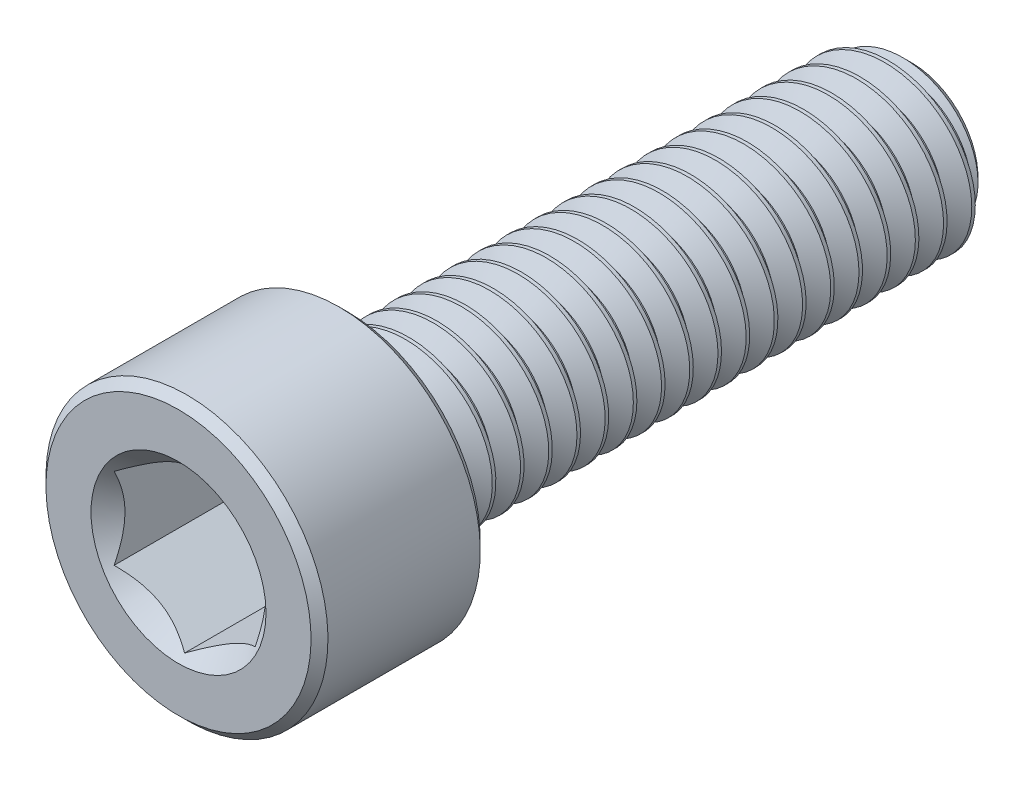
SolidWorks part; units mm, degrees
ref_plane "Front Plane" through (0, 0, 0) normal (0, 0, 1) x (1, 0, 0)
ref_plane "Top Plane" through (0, 0, 0) normal (0, 1, 0) x (1, 0, 0)
ref_plane "Right Plane" through (0, 0, 0) normal (1, 0, 0) x (0, 0, -1)
sketch "Sketch1" plane through (0, 0, 0) normal (1, 0, 0) x (0, 0, -1)
  line L0 (-13, 0) -> (13, 0) construction
  line L1 (13, 0) -> (13, 2.3505) construction
  line L2 (13, 2.3505) -> (12.3505, 3) construction
  line L3 (12.3505, 3) -> (12.25, 3) construction
  line L4 (12.25, 3) -> (-7, 3) construction
  line L5 (-7, 3) -> (-7, 5) construction
  line L6 (-7, 5) -> (-13, 5) construction
  line L7 (-13, 5) -> (-13, 0) construction
  line L8 (13, 2.3505) -> (13, 3) construction
  line L9 (12.9375, 3.1083) -> (13.4375, 2.2422) construction
  line L10 (13.4375, 2.2422) -> (13.9375, 3.1083) construction
  line L11 (13.9375, 3.1083) -> (12.9375, 3.1083) construction
  line L12 (13.4375, 3.1083) -> (13.4375, 3) construction
  line L13 (13.4375, 2.2422) -> (13.4375, 2.3505) construction
  line L14 (13.375, 2.3505) -> (13.5, 2.3505) construction
  line L15 (13, 3) -> (13.875, 3) construction
  line L16 (12.9688, 3.0541) -> (13.9063, 3.0541) construction
  line L17 (13, 0) -> (13, -3) construction
  line L18 (-7.3, 5) -> (-7, 4.7) construction
  line L19 (-12.7, 5) -> (-13, 4.7) construction
  line L20 (-7, 3) -> (-7, 0) construction
  line L21 (-7, 1.5) -> (-0.3333, 1.5) construction
  line L22 (-0.3333, 1.5) -> (6.3333, 1.5) construction
  line L23 (6.3333, 1.5) -> (13, 1.5) construction
  line L24 (-0.3333, 1.5) -> (-0.3333, 3) construction
  line L25 (-0.3333, 3) -> (-0.3333, 5) construction
  line L26 (6.3333, 1.5) -> (6.3333, 5) construction
  point P0 (-13, 2.5)
  point P3 (10.5, 3)
  point P4 (0, 0)
  point P18 (6.3333, 3)
  point P22 (13.4375, 2.3505)
  point P24 (12.25, 3)
  point P25 (13.4375, 3)
  point P28 (13.4375, 3.0541)
  point P29 (10.5, -3)
  point P30 (-0.3333, 3)
  point P31 (-10, 5)
  point P37 (-8.05, 5)
  point P38 (-12.55, 5)
  point P45 (-0.3333, 1.5)
  point P46 (6.3333, 1.5)
  dimension "D2" = 0.125
  dimension "D7" = 0.3
  dimension "D8" = 0.3
  dimension "D9" = 0.3
  dimension "D10" = 0.15
  dimension "D11" = 0.75
  dimension "Drive Size" = 5
  dimension "Head Diameter" = 10
  dimension "Head Height" = 6
  dimension "Thread Pitch" = 1
  dimension "Thread Dia" = 6
  dimension "Length" = 20
  dimension "D12" = 0.75
  dimension "D4" = 2.5
  dimension "D3" = 45
sketch "Sketch2" plane through (0, 0, 0) normal (1, 0, 0) x (0, 0, -1)
  line L0 (-13, 0) -> (-13, 4.7)
  line L1 (-12.7, 5) -> (-7.3, 5)
  line L2 (-7, 4.7) -> (-7, 3.3)
  line L4 (12.3505, 3) -> (13, 2.3505)
  line L5 (13, 2.3505) -> (13, 0)
  line L6 (-7, 5) -> (-13, 5) construction
  line L7 (13, 0) -> (-13, 0)
  line L8 (-12.7, 5) -> (-13, 4.7) construction
  line L10 (-12.7, 5) -> (-13, 4.7)
  line L14 (-7.3, 5) -> (-7, 4.7) construction
  line L16 (-7.3, 5) -> (-7, 4.7)
  line L17 (-7, 3) -> (-7, 5) construction
  line L19 (-6.7, 3) -> (12.3505, 3)
  line L20 (12.25, 3) -> (-7, 3) construction
  arc A1 (-7, 3.3) -> (-6.7, 3) centre (-6.7, 3.3) ccw
  dimension "D3" = 0.3
revolve "Revolve1" add sketch "Sketch2" angle 360 about L7
sketch "Sketch3" plane through (0, 0, 13) normal (0, 0, 1) x (1, 0, 0)
  line L1 (2.5, -1.4434) -> (2.5, 1.4434)
  line L2 (2.5, 1.4434) -> (0, 2.8868)
  line L3 (0, 2.8868) -> (-2.5, 1.4434)
  line L4 (-2.5, 1.4434) -> (-2.5, -1.4434)
  line L5 (-2.5, -1.4434) -> (0, -2.8868)
  line L6 (0, -2.8868) -> (2.5, -1.4434)
  circle A0 centre (0, 0) radius 2.5 construction
  circle A1 centre (0, 0) radius 5 construction
  circle A2 centre (0, 0) radius 5 construction
  circle A3 centre (0, 0) radius 2.8868 construction
  point P13 (0, 0)
  dimension "D1" = 5.7735
extrude "Cut-Extrude1" cut sketch "Sketch3" against normal offset from surface (5 mm away) 1 up to face at (0, 4.7, 7)
sketch "Sketch4" plane through (0, 0, 13) normal (0, 0, 1) x (1, 0, 0)
  circle A0 centre (0, 0) radius 3.1033
  dimension "D1" = 6.2065
extrude "Cut-Extrude2" cut sketch "Sketch4" against normal up to vertex (3 mm away) draft 45 up to point (0, 5, 10)
sketch "Sketch11" plane through (0, 0, 0) normal (1, 0, 0) x (0, 0, -1)
  line L0 (-13, 0) -> (13, 0) construction
  line L1 (-13, 0) -> (13, 0) construction
  line L2 (-3.25, 0) -> (-3.25, 3) construction
  line L3 (12.25, 3) -> (-7, 3) construction
  line L4 (9.25, 0) -> (9.25, 3) construction
  line L6 (13, 2.3505) -> (13, 3) construction
  point P2 (-3.25, 0)
  point P3 (9.25, 0)
  dimension "D1" = 3.75
  dimension "D2" = 3.75
sketch "Sketch6" plane through (0, 0, -13) normal (0, 0, -1) x (-1, 0, 0)
  circle A0 centre (0, 0) radius 3
curve "Helix/Spiral1" pitch 1 height 21 radius 3 centre (0, 0, -13) axis (0, 0, 1) start towards (0, 1, 0)
sketch "Sketch10" plane through (0, 0, 0) normal (1, 0, 0) x (0, 0, -1)
  line L0 (-6.7, -5) -> (-6.7, 5)
  line L5 (-13, 0) -> (13, 0) construction
  line L6 (-6.7, 3) -> (-6.7, -3) construction
  point P3 (-6.7, 0)
split "Split1" trim tools "Sketch10" bodies to split 106 resulting bodies 114 115
sketch "Sketch7" plane through (0, 0, 0) normal (1, 0, 0) x (0, 0, -1)
  line L0 (12.9688, 3.0541) -> (13.9063, 3.0541)
  line L1 (13.9063, 3.0541) -> (13.5, 2.3505)
  line L2 (13.5, 2.3505) -> (13.375, 2.3505)
  line L3 (13.375, 2.3505) -> (12.9688, 3.0541)
sweep "Cut-Sweep1" cut profiles "Sketch7" path "Helix/Spiral1" align with end faces yes
sketch "Sketch8" plane through (0, 0, 0) normal (1, 0, 0) x (0, 0, -1)
  line L0 (-7, 0) -> (-7, 3)
  line L1 (-6.7, -3) -> (-6.7, 3) construction
  line L2 (-7, 3) -> (-6.7, 3)
  line L4 (-6.7, 3) -> (-4.9679, 0)
  line L5 (-4.9679, 0) -> (-7, 0)
  line L6 (12.25, 3) -> (-7, 3) construction
  line L7 (-13, 0) -> (13, 0) construction
  dimension "D1" = 60
revolve "Revolve2" add sketch "Sketch8" angle 360 about L5
equation "\"D2@Sketch1\" = \"Thread Pitch@Sketch1\" / 8"
equation "\"D4@Helix/Spiral1\" = \"Thread Pitch@Sketch1\""
equation "\"D7@Sketch1\" = \"Head Height@Sketch1\" * .05"
equation "\"D8@Sketch1\"=\"D7@Sketch1\""
equation "\"D9@Sketch1\"=\"D7@Sketch1\""
equation "\"D10@Sketch1\"=\"D7@Sketch1\"/2"
equation "\"D11@Sketch1\"=\"D10@Sketch1\"*5"
equation "\"D4@Sketch1\"=\"Thread Pitch@Sketch1\"*2.5"
equation "\"D12@Sketch1\"=\"Thread Pitch@Sketch1\"*.75"
equation "\"D3@Helix/Spiral1\"=\"Length@Sketch1\"+\"Thread Pitch@Sketch1\""
equation "\"D3@Sketch2\"=\"Thread Dia@Sketch1\"*0.05"
equation "\"D1@Sketch11\"=\"Length@Sketch1\"*0.1875"
equation "\"D2@Sketch11\"=\"D1@Sketch11\""
equation "\"D1@Sketch4\"=\"D1@Sketch3\"*1.075"
